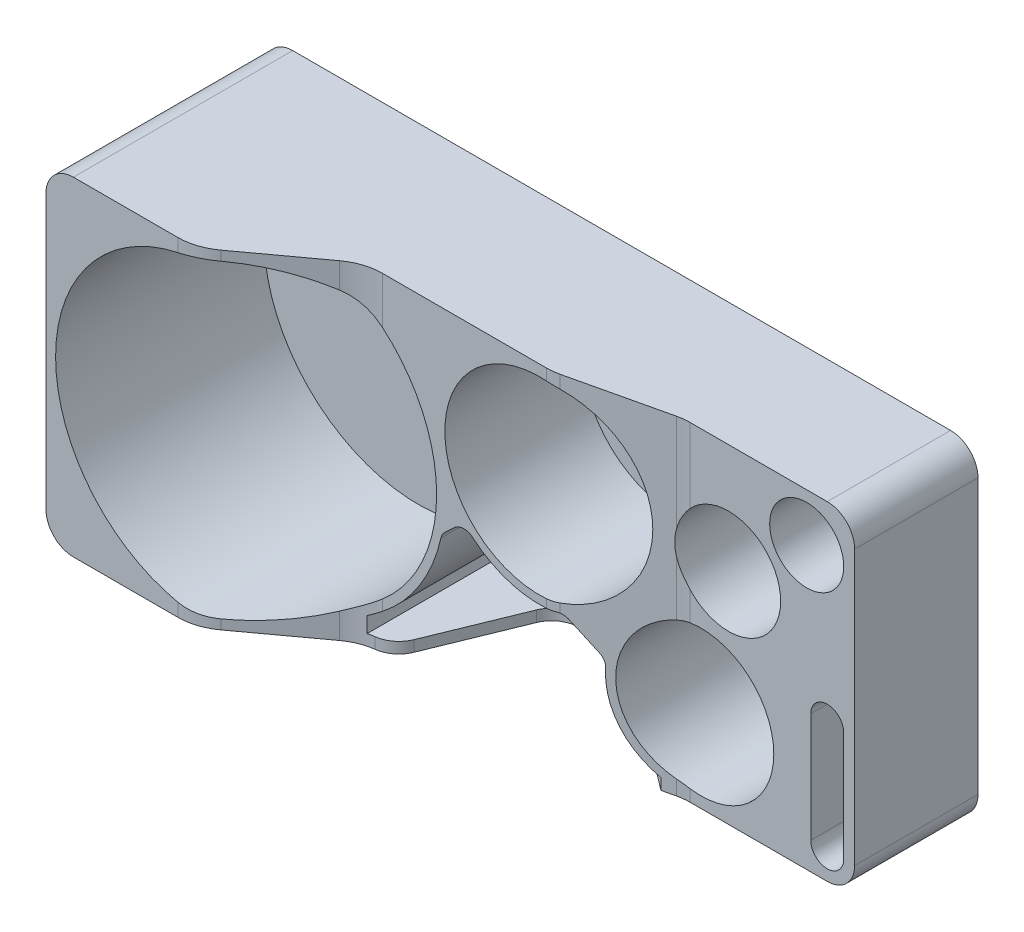
SolidWorks part; units mm, degrees
ref_plane "Front Plane" through (0, 0, 0) normal (1, 0, 0) x (0, 1, 0)
ref_plane "Top Plane" through (0, 0, 0) normal (0, 0, 1) x (0, 1, 0)
ref_plane "Right Plane" through (0, 0, 0) normal (0, 1, 0) x (-1, 0, 0)
sketch "Sketch1" plane through (0, 0, 0) normal (0, 0, 1) x (0, 1, 0)
  line L1 (30, -65) -> (-30, -65)
  line L2 (30, -65) -> (30, 65)
  line L3 (30, 65) -> (-30, 65)
  line L4 (-30, -65) -> (-30, 65)
  line L5 (30, -65) -> (-30, 65) construction
  line L6 (30, 65) -> (-30, -65) construction
  point P0 (0, 0)
  dimension "D1" = 60
  dimension "D2" = 130
extrude "Boss-Extrude1" add sketch "Sketch1" along normal blind 40
sketch "Sketch2" plane through (0, 0, 40) normal (0, 0, 1) x (1, 0, 0)
  line L0 (-65, 0) -> (65, 0) construction
  line L1 (-65, 30) -> (-65, -30) construction
  line L2 (65, -30) -> (65, 30) construction
  line L3 (65, 30) -> (-65, 30) construction
  line L4 (-65, -30) -> (65, -30) construction
  line L5 (60, -5) -> (60, -25) construction
  line L6 (63, -5) -> (63, -25)
  line L7 (57, -5) -> (57, -25)
  circle A0 centre (-35, 0) radius 28.25
  circle A1 centre (37, -14.75) radius 13.25
  circle A2 centre (12, 10.75) radius 17.25
  circle A3 centre (56.25, 21.25) radius 6.75
  circle A4 centre (42, 10) radius 9.5
  arc A6 (63, -5) -> (57, -5) centre (60, -5) ccw
  arc A7 (57, -25) -> (63, -25) centre (60, -25) ccw
  point P2 (56.25, 28)
  point P19 (51.5, 10)
  point P20 (49.8258, 15.3858)
  point P21 (51.0599, 16.9343)
  point P22 (50.25, -14.75)
  point P23 (37, -28)
  point P26 (12, 28)
  point P29 (60, -15)
  point P34 (58.6833, -14.75)
  point P35 (15, 10.75)
  point P40 (63, 21.25)
  dimension "D1" = 56.5
  dimension "D2" = 30
  dimension "D3" = 26.5
  dimension "D4" = 34.5
  dimension "D5" = 13.5
  dimension "D6" = 19
  dimension "D7" = 2
  dimension "D9" = 10
  dimension "D10" = 25
  dimension "D8" = 2
  dimension "D11" = 2
  dimension "D12" = 2
  dimension "D13" = 12
  dimension "D14" = 30
  dimension "D15" = 6
  dimension "D16" = 20
  dimension "D17" = 2
  dimension "D18" = 15
extrude "Cut-Extrude1" cut sketch "Sketch2" against normal blind 38
sketch "Sketch11" plane through (0, 0, 0) normal (0, 1, 0) x (-1, 0, 0)
  line L0 (37.6626, 40) -> (-65, 40)
  line L1 (-65, 40) -> (65, 40) construction
  line L2 (-65, 40) -> (-65, 22.5)
  line L3 (-65, 40) -> (-65, 0) construction
  line L4 (-65, 22.5) -> (-33.8575, 22.5)
  line L5 (-33.8575, 22.5) -> (-14.423, 27)
  line L6 (-14.423, 27) -> (19.9144, 27)
  line L7 (19.9144, 27) -> (37.6626, 40)
  line L8 (63.25, 40) -> (6.75, 40) construction
  line L9 (-65, 0) -> (65, 0) construction
  point P11 (37.6626, 40)
  point P12 (0, 0)
  point P17 (-27.3649, 27.4655)
  point P18 (19.9144, 25.7759)
  point P19 (-14.423, 25)
  dimension "D1" = 22.5
  dimension "D2" = 27
extrude "Cut-Extrude9" cut sketch "Sketch11" against normal through all both and the other way through all
sketch "Sketch12" plane through (0, 0, 0) normal (0, 0, 1) x (0, 1, 0)
  line L3 (-25.1531, 19.1134) -> (-28, 19.1134)
  line L4 (-5.7353, 5.8081) -> (-1.9874, 1.7594)
  line L5 (-28, -33.8575) -> (-28, -14.423)
  line L6 (-28, -14.423) -> (-28, 19.9144)
  line L7 (-28, -30.5193) -> (-28, -14.423)
  line L8 (-28, -14.423) -> (-28, 19.1134)
  line L9 (-7.5689, -15.9976) -> (-12.6145, -22.4054)
  arc A2 (-25.1531, 19.1134) -> (25.1531, 19.1134) centre (0, 35) ccw
  arc A3 (-25.1531, 19.1134) -> (-5.7353, 5.8081) centre (0, 35) ccw
  arc A4 (-0.4208, -33.5017) -> (-29.0792, -33.5017) centre (-14.75, -37) ccw
  circle A5 centre (10.75, -12) radius 18.75
  arc A6 (-1.9874, 1.7594) -> (-7.5689, -15.9976) centre (10.75, -12) ccw
  arc A7 (-12.6145, -22.4054) -> (-28, -30.5193) centre (-14.75, -37) ccw
  point P9 (-2.074, 1.6787)
  point P11 (-5.7353, 5.8081)
  dimension "D1" = 1.5
  dimension "D2" = 1.5
  dimension "D3" = 1.5
  dimension "D4" = 2
extrude "Cut-Extrude10" cut sketch "Sketch12" along normal through all from offset 2
sketch "Sketch13" plane through (0, -30, 0) normal (0, -1, 0) x (1, 0, 0)
  line L0 (-15.1125, 27) -> (35.3513, 27)
  line L1 (14.423, 27) -> (-19.9144, 27) construction
  line L2 (35.3513, 27) -> (6.3641, 5)
  line L3 (6.3641, 5) -> (-6.1359, 5)
  line L4 (-6.1359, 5) -> (-15.1125, 27)
  line L5 (-19.1134, 2) -> (30.5193, 2) construction
  point P0 (35.3513, 27)
  point P4 (-14.0035, 27)
  dimension "D1" = 3
  dimension "D2" = 12.5
  dimension "D3" = 75
extrude "Cut-Extrude11" cut sketch "Sketch13" against normal up to next
fillet "Fillet8" radius 5 4 edges at (-65, -30, 20) (-65, 30, 20) (65, 30, 11.25) (65, -30, 11.25)
fillet "Fillet9" radius 10 9 edges at (14.423, 28.9145, 27) (14.423, -7.0859, 27) (33.8575, -28.811, 22.5) (33.8575, 1.6141, 22.5) (33.8575, 22.4469, 22.5) (-37.6626, 29.0621, 40) (-37.6626, -29.0621, 40) (-19.9144, -26.9425, 27) (-19.9144, 26.9425, 27) tangent propagation no
fillet "Fillet10" radius 2.5 4 edges at (22.4054, -12.6145, 13.5758) (15.9976, -7.5689, 14.3177) (-1.7594, -1.9874, 14.5) (-5.8081, -5.7353, 14.5)
fillet "Fillet11" radius 5 3 edges at (6.3641, -29, 5) (-6.1359, -29, 5) (-15.1125, -29, 27)
